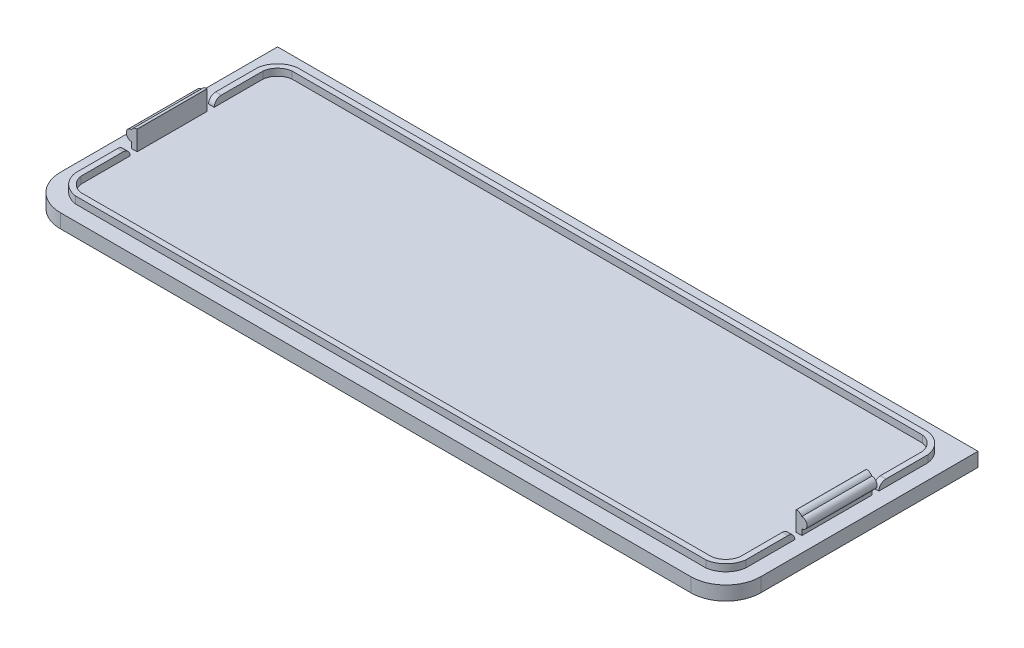
SolidWorks part; units mm, degrees
ref_plane "前视基准面" through (0, 0, 0) normal (0, 0, 1) x (1, 0, 0)
ref_plane "上视基准面" through (0, 0, 0) normal (0, 1, 0) x (1, 0, 0)
ref_plane "右视基准面" through (0, 0, 0) normal (1, 0, 0) x (0, 0, -1)
sketch "zero" plane through (0, 0, 0) normal (0, 1, 0) x (1, 0, 0)
  line L1 (-29.5, 15) -> (29.5, 15)
  line L2 (-32.5, 12) -> (-32.5, -12)
  line L3 (-29.5, -15) -> (29.5, -15)
  line L4 (32.5, 12) -> (32.5, -12)
  line L5 (-32.5, 15) -> (32.5, -15) construction
  line L6 (-32.5, -15) -> (32.5, 15) construction
  line L7 (-25.7, -15) -> (-14.5, -15)
  line L8 (-25.7, -15) -> (-25.7, -9.6569)
  line L9 (-25.7, -9.6569) -> (-14.5, -9.6569)
  line L10 (-14.5, -15) -> (-14.5, -9.6569)
  line L11 (5.2, -15) -> (12.7, -15)
  line L12 (5.2, -15) -> (5.2, -11)
  line L13 (5.2, -11) -> (12.7, -11)
  line L14 (12.7, -15) -> (12.7, -11)
  line L15 (17.8, -15) -> (25.3, -15)
  line L16 (17.8, -15) -> (17.8, -11)
  line L17 (17.8, -11) -> (25.3, -11)
  line L18 (25.3, -15) -> (25.3, -11)
  line L19 (-32.5, 7.7) -> (-19.5, 7.7)
  line L20 (-32.5, 7.7) -> (-32.5, -4.3)
  line L21 (-32.5, -4.3) -> (-19.5, -4.3)
  line L22 (-19.5, 7.7) -> (-19.5, -4.3)
  line L23 (-25.5, 14) -> (25.5, 14)
  line L24 (-25.5, 14) -> (-25.5, 8.8)
  line L25 (-25.5, 8.8) -> (25.5, 8.8)
  line L26 (25.5, 14) -> (25.5, 8.8)
  line L27 (-19.5, 7.2329) -> (-35.5, 7.2329)
  line L28 (-19.5, 7.2329) -> (-19.5, -3.7671)
  line L29 (-19.5, -3.7671) -> (-35.5, -3.7671)
  line L30 (-35.5, 7.2329) -> (-35.5, -3.7671)
  arc A0 (29.5, -15) -> (32.5, -12) centre (29.5, -12) ccw
  arc A1 (29.5, 15) -> (32.5, 12) centre (29.5, 12) cw
  arc A2 (-32.5, -12) -> (-29.5, -15) centre (-29.5, -12) ccw
  arc A3 (-29.5, 15) -> (-32.5, 12) centre (-29.5, 12) ccw
  circle A4 centre (-29, 11.4) radius 3
  circle A5 centre (-29, -11.5) radius 3
  circle A6 centre (29, 11.4) radius 3
  circle A7 centre (29, -11.5) radius 3
  circle A8 centre (-29, 11.4) radius 1.375
  circle A9 centre (-29, -11.5) radius 1.375
  circle A10 centre (29, -11.5) radius 1.375
  circle A11 centre (29, 11.4) radius 1.375
  point P0 (0, 0)
  dimension "D3" = 3
  dimension "D4" = 6
  dimension "D9" = 2.75
  dimension "D1" = 65
  dimension "D2" = 30
  dimension "D5" = 3.6
  dimension "D6" = 3.5
  dimension "D7" = 3.5
  dimension "D8" = 3.5
  dimension "D10" = 12
  dimension "D11" = 7.3
  dimension "D12" = 13
  dimension "D13" = 11.2
  dimension "D14" = 6.8
  dimension "D15" = 19.7
  dimension "D16" = 7.5
  dimension "D17" = 7.5
  dimension "D18" = 5.1
  dimension "D19" = 4
  dimension "D20" = 5.2
  dimension "D21" = 7
  dimension "D22" = 7
  dimension "D23" = 1
  dimension "D24" = 11
  dimension "D25" = 16
sketch "sugar" plane through (0, 0, 0) normal (0, 1, 0) x (1, 0, 0)
  line L1 (-29.5, 15) -> (29.5, 15)
  line L2 (-32.5, 12) -> (-32.5, -12)
  line L3 (-29.5, -15) -> (29.5, -15)
  line L4 (32.5, 12) -> (32.5, -12)
  line L5 (-32.5, 15) -> (32.5, -15) construction
  line L6 (-32.5, -15) -> (32.5, 15) construction
  line L7 (23.5, -11.5) -> (19.5, -11.5)
  line L8 (23.5, -11.5) -> (23.5, -13.9082)
  line L9 (23.5, -13.9082) -> (19.5, -13.9082)
  line L10 (19.5, -11.5) -> (19.5, -13.9082)
  line L11 (16, -11.0071) -> (8.5, -11.0071)
  line L12 (16, -11.0071) -> (16, -15)
  line L13 (16, -15) -> (8.5, -15)
  line L14 (8.5, -11.0071) -> (8.5, -15)
  line L15 (20.5, -13.9082) -> (22.5, -13.9082)
  line L16 (20.5, -13.9082) -> (20.5, -14.8173)
  line L17 (20.5, -14.8173) -> (22.5, -14.8173)
  line L18 (22.5, -13.9082) -> (22.5, -14.8173)
  arc A0 (29.5, 15) -> (32.5, 12) centre (29.5, 12) cw
  arc A1 (29.5, -15) -> (32.5, -12) centre (29.5, -12) ccw
  arc A2 (-32.5, -12) -> (-29.5, -15) centre (-29.5, -12) ccw
  arc A3 (-29.5, 15) -> (-32.5, 12) centre (-29.5, 12) ccw
  circle A4 centre (-29, 11.4) radius 3
  circle A5 centre (-29, 11.4) radius 1.375
  circle A6 centre (-29, -11.5) radius 3
  circle A7 centre (-29, -11.5) radius 1.375
  circle A8 centre (29, 11.4) radius 3
  circle A9 centre (29, 11.4) radius 1.375
  circle A10 centre (29, -11.5) radius 3
  circle A11 centre (29, -11.5) radius 1.375
  dimension "D3" = 3
  dimension "D1" = 65
  dimension "D2" = 30
  dimension "D4" = 9
  dimension "D5" = 4
  dimension "D6" = 3.5
  dimension "D7" = 7.5
  dimension "D8" = 2
  dimension "D9" = 1
sketch "case" plane through (0, 0, 0) normal (0, 1, 0) x (1, 0, 0)
  line L0 (-51.5422, 13) -> (-51.5422, 18)
  line L1 (-46.5422, 18) -> (43.4578, 18)
  line L2 (-51.5422, 13) -> (-51.5422, -13)
  line L3 (-46.5422, -18) -> (43.4578, -18)
  line L4 (48.4578, 13) -> (48.4578, -13)
  line L5 (-51.5422, 18) -> (48.4578, -18) construction
  line L6 (-51.5422, -18) -> (48.4578, 18) construction
  line L7 (-51.5422, 18) -> (-46.5422, 18)
  line L8 (43.4578, 18) -> (48.4578, 18)
  line L9 (48.4578, 18) -> (48.4578, 13)
  arc A0 (-51.5422, -13) -> (-46.5422, -18) centre (-46.5422, -13) ccw
  arc A1 (43.4578, -18) -> (48.4578, -13) centre (43.4578, -13) ccw
  point P0 (-1.5422, 0)
  point P3 (-1.5422, 0)
  dimension "D3" = 5
  dimension "D1" = 100
  dimension "D2" = 36
extrude "凸台-拉伸2" add sketch "case" along normal blind 2
sketch "草图2" plane through (0, 0, 0) normal (0, 1, 0) x (1, 0, 0)
  line L4 (-34.0422, -15.05) -> (30.9578, -15.05)
  line L5 (33.0078, -13) -> (33.0078, 13)
  line L6 (30.9578, 15.05) -> (-34.0422, 15.05)
  line L7 (-36.0922, 13) -> (-36.0922, -13)
  line L12 (33.8078, -13) -> (33.8078, 13)
  line L13 (30.9578, 15.85) -> (-34.0422, 15.85)
  line L14 (-36.8922, 13) -> (-36.8922, -13)
  line L15 (-34.0422, -15.85) -> (30.9578, -15.85)
  arc A4 (30.9578, -15.05) -> (33.0078, -13) centre (30.6303, -12.6725) ccw
  arc A5 (33.0078, 13) -> (30.9578, 15.05) centre (30.6303, 12.6725) ccw
  arc A6 (-34.0422, 15.05) -> (-36.0922, 13) centre (-33.7147, 12.6725) ccw
  arc A7 (-36.0922, -13) -> (-34.0422, -15.05) centre (-33.7147, -12.6725) ccw
  arc A12 (30.9578, -15.85) -> (33.8078, -13) centre (30.535, -12.5772) ccw
  arc A13 (33.8078, 13) -> (30.9578, 15.85) centre (30.535, 12.5772) ccw
  arc A14 (-34.0422, 15.85) -> (-36.8922, 13) centre (-33.6194, 12.5772) ccw
  arc A15 (-36.8922, -13) -> (-34.0422, -15.85) centre (-33.6194, -12.5772) ccw
ref_plane "基准面1" through (0, 2, 0) normal (0, 1, 0) x (1, 0, 0)
sketch "草图3" plane through (0, 2, 0) normal (0, 1, 0) x (1, 0, 0)
  line L8 (-46.5422, -15.05) -> (43.4578, -15.05)
  line L9 (45.5078, -13) -> (45.5078, 13)
  line L10 (43.4578, 15.05) -> (-46.5422, 15.05)
  line L11 (-48.5922, 13) -> (-48.5922, -13)
  line L16 (-49.3922, 13) -> (-49.3922, -13)
  line L17 (-46.5422, -15.85) -> (43.4578, -15.85)
  line L18 (46.3078, -13) -> (46.3078, 13)
  line L19 (43.4578, 15.85) -> (-46.5422, 15.85)
  arc A8 (43.4578, -15.05) -> (45.5078, -13) centre (43.1303, -12.6725) ccw
  arc A9 (45.5078, 13) -> (43.4578, 15.05) centre (43.1303, 12.6725) ccw
  arc A10 (-46.5422, 15.05) -> (-48.5922, 13) centre (-46.2147, 12.6725) ccw
  arc A11 (-48.5922, -13) -> (-46.5422, -15.05) centre (-46.2147, -12.6725) ccw
  arc A16 (-49.3922, -13) -> (-46.5422, -15.85) centre (-46.1194, -12.5772) ccw
  arc A17 (43.4578, -15.85) -> (46.3078, -13) centre (43.035, -12.5772) ccw
  arc A18 (46.3078, 13) -> (43.4578, 15.85) centre (43.035, 12.5772) ccw
  arc A19 (-46.5422, 15.85) -> (-49.3922, 13) centre (-46.1194, 12.5772) ccw
extrude "凸台-拉伸4" add sketch "草图3" along normal blind 1
ref_plane "基准面3" through (46.3078, 0, 0) normal (1, 0, 0) x (0, 0, -1)
sketch "草图7" plane through (0, 2, 0) normal (0, 1, 0) x (1, 0, 0)
  line L0 (-49.3922, 13) -> (-49.3922, -13) construction
  line L1 (-49.3922, 5) -> (-48.5922, 5)
  line L2 (-49.3922, 5) -> (-49.3922, -5)
  line L3 (-49.3922, -5) -> (-48.5922, -5)
  line L4 (-48.5922, 5) -> (-48.5922, -5)
  line L5 (-48.5922, 13) -> (-48.5922, -13) construction
  line L8 (-51.5422, 2.5) -> (-49.3922, 0) construction
  line L10 (-51.5422, 18) -> (-51.5422, -13) construction
  line L11 (-49.3922, 0) -> (-48.5922, 0) construction
  point P10 (-48.5922, 0)
  dimension "D1" = 5
  dimension "D2" = 10
extrude "凸台-拉伸8" add sketch "草图7" along normal blind 2.8
ref_plane "基准面5" through (0, 0, 5) normal (0, 0, 1) x (1, 0, 0)
sketch "草图8" plane through (0, 0, 5) normal (0, 0, 1) x (1, 0, 0)
  line L0 (-46.5422, 2) -> (-51.5422, 2) construction
  line L1 (-49.3922, 4.8) -> (-49.3922, 3) construction
  circle A0 centre (-49.3922, 3.6) radius 0.75
  dimension "D1" = 1.5
  dimension "D2" = 1.6
  dimension "D3" = 0
extrude "凸台-拉伸9" add sketch "草图8" against normal blind 10
fillet "圆角1" radius 0.85 1 edges at (-49.3922, 4.8, 0)
ref_plane "基准面7" through (-49.3922, 0, 0) normal (-1, 0, 0) x (0, 0, 1)
sketch "草图11" plane through (-49.3922, 0, 0) normal (-1, 0, 0) x (0, 0, 1)
  line L0 (-13, 2) -> (13, 2) construction
  line L1 (5, 3) -> (6, 3)
  line L2 (5, 3) -> (5, 2)
  line L3 (5, 2) -> (6, 2)
  line L4 (6, 3) -> (6, 2)
  line L6 (-5, 3) -> (-6, 3)
  line L7 (-5, 3) -> (-5, 2)
  line L8 (-5, 2) -> (-6, 2)
  line L9 (-6, 3) -> (-6, 2)
  dimension "D1" = 1
  dimension "D2" = 1
extrude "切除-拉伸1" cut sketch "草图11" against normal blind 1.2
fillet "圆角2" radius 1 2 edges at (-48.9922, 3, 6) (-48.9922, 3, -6)
ref_plane "基准面8" through (0, 0, 0) normal (0, -1, 0) x (-1, 0, 0)
sketch "草图13" plane through (0, 3, 0) normal (0, 1, 0) x (1, 0, 0)
  line L1 (45.5078, 5) -> (46.3078, 5)
  line L2 (45.5078, 5) -> (45.5078, -5)
  line L3 (45.5078, -5) -> (46.3078, -5)
  line L4 (46.3078, 5) -> (46.3078, -5)
  dimension "D1" = 10
extrude "凸台-拉伸10" add sketch "草图13" along normal blind 1.8
sketch "草图14" plane through (0, 0, 5) normal (0, 0, 1) x (1, 0, 0)
  line L0 (46.3078, 2) -> (43.4578, 2) construction
  line L1 (46.3078, 4.8) -> (46.3078, 3) construction
  circle A0 centre (46.3078, 3.6) radius 0.75
  dimension "D2" = 1.5
  dimension "D1" = 1.6
  dimension "D3" = 0
extrude "凸台-拉伸11" add sketch "草图14" against normal blind 10
fillet "圆角3" radius 0.85 1 edges at (46.3078, 4.8, 0)
sketch "草图15" plane through (0, 3, 0) normal (0, 1, 0) x (1, 0, 0)
  line L0 (46.3078, 5) -> (46.3078, 13) construction
  line L1 (45.5078, 5) -> (46.3078, 5)
  line L2 (45.5078, 5) -> (45.5078, 6)
  line L3 (45.5078, 6) -> (46.3078, 6)
  line L4 (46.3078, 5) -> (46.3078, 6)
  line L5 (46.3078, -13) -> (46.3078, -5) construction
  line L6 (45.5078, -5) -> (46.3078, -5)
  line L7 (45.5078, -5) -> (45.5078, -6)
  line L8 (45.5078, -6) -> (46.3078, -6)
  line L9 (46.3078, -5) -> (46.3078, -6)
  dimension "D1" = 1
  dimension "D2" = 1
extrude "切除-拉伸3" cut sketch "草图15" against normal blind 1
fillet "圆角4" radius 1 2 edges at (45.9078, 3, 6) (45.9078, 3, -6)
ref_plane "Plan1" through (43.4578, 2, -15.85) normal (-1, 0, 0) x (0, 0, 1)
